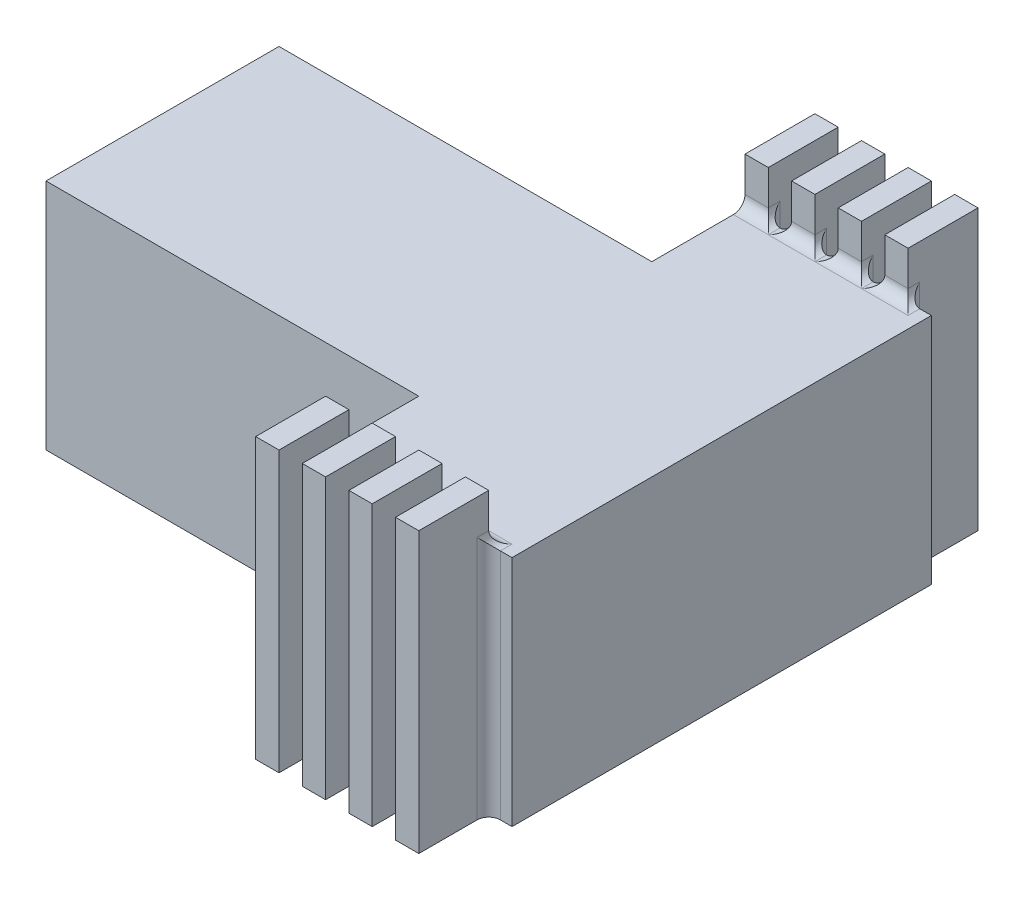
SolidWorks part; units mm, degrees
ref_plane "Front Plane" through (0, 0, 0) normal (0, 0, 1) x (1, 0, 0)
ref_plane "Top Plane" through (0, 0, 0) normal (0, 1, 0) x (1, 0, 0)
ref_plane "Right Plane" through (0, 0, 0) normal (1, 0, 0) x (0, 0, -1)
sketch "Sketch1" plane through (0, 0, 0) normal (0, 1, 0) x (1, 0, 0)
  line L0 (80, 50) -> (80, 70)
  line L1 (0, 0) -> (80, 0)
  line L2 (0, 0) -> (0, 50)
  line L3 (0, 50) -> (80, 50)
  line L5 (80, 70) -> (120, 70)
  line L6 (80, 0) -> (80, -20)
  line L7 (80, -20) -> (120, -20)
  line L8 (120, -20) -> (120, 70)
  dimension "D1" = 50
  dimension "D2" = 80
  dimension "D3" = 40
  dimension "D4" = 20
extrude "Boss-Extrude1" add sketch "Sketch1" along normal blind 50
sketch "Sketch2" plane through (0, 50, 0) normal (0, 1, 0) x (1, 0, 0)
  line L1 (80, -20) -> (85, -20)
  line L2 (80, -20) -> (80, -35)
  line L3 (80, -35) -> (85, -35)
  line L4 (85, -20) -> (85, -35)
  line L5 (0, 25) -> (120, 25) construction
  line L6 (0, 50) -> (0, 0) construction
  line L7 (120, -20) -> (120, 70) construction
  line L8 (90, -20) -> (90, -35)
  line L9 (90, -20) -> (95, -20)
  line L10 (95, -20) -> (95, -35)
  line L11 (90, -35) -> (95, -35)
  line L12 (100, -20) -> (100, -35)
  line L13 (100, -20) -> (105, -20)
  line L14 (105, -20) -> (105, -35)
  line L15 (100, -35) -> (105, -35)
  line L16 (110, -20) -> (110, -35)
  line L17 (110, -20) -> (115, -20)
  line L18 (115, -20) -> (115, -35)
  line L19 (110, -35) -> (115, -35)
  line L20 (110, 70) -> (115, 70)
  line L21 (115, 70) -> (115, 85)
  line L22 (110, 85) -> (115, 85)
  line L23 (110, 70) -> (110, 85)
  line L24 (100, 70) -> (105, 70)
  line L25 (105, 70) -> (105, 85)
  line L26 (100, 85) -> (105, 85)
  line L27 (100, 70) -> (100, 85)
  line L28 (90, 70) -> (95, 70)
  line L29 (95, 70) -> (95, 85)
  line L30 (90, 85) -> (95, 85)
  line L31 (90, 70) -> (90, 85)
  line L32 (80, 85) -> (85, 85)
  line L33 (85, 70) -> (85, 85)
  line L34 (80, 70) -> (85, 70)
  line L35 (80, 70) -> (80, 85)
  dimension "D1" = 5
  dimension "D2" = 15
  dimension "D3" = 5
  dimension "D4" = 4
extrude "Boss-Extrude2" add sketch "Sketch2" along normal blind 10 and the other way up to surface (50 mm away) other way up to face at (70, 0, -25)
fillet "Fillet1" radius 2.5 14 edges at (90, 25, -70) (100, 25, -70) (110, 25, -70) (85, 25, -70) (95, 25, -70) (105, 25, -70) (115, 25, -70) (90, 25, 20) (100, 25, 20) (110, 25, 20) (115, 25, 20) (105, 25, 20) (95, 25, 20) (85, 25, 20)
fillet "Fillet2" radius 2.5 8 edges at (112.5, 50, -70) (102.5, 50, -70) (92.5, 50, -70) (82.5, 50, -70) (82.5, 50, 20) (92.5, 50, 20) (102.5, 50, 20) (112.5, 50, 20)
fillet "Fillet4" radius 2.5 14 edges at (110, 50, -70) (100, 50, -70) (90, 50, -70) (110, 50, 20) (100, 50, 20) (90, 50, 20) (115, 50, -70) (105, 50, -70) (95, 50, -70) (85, 50, -70) (85, 50, 20) (95, 50, 20) (105, 50, 20) (115, 50, 20)
